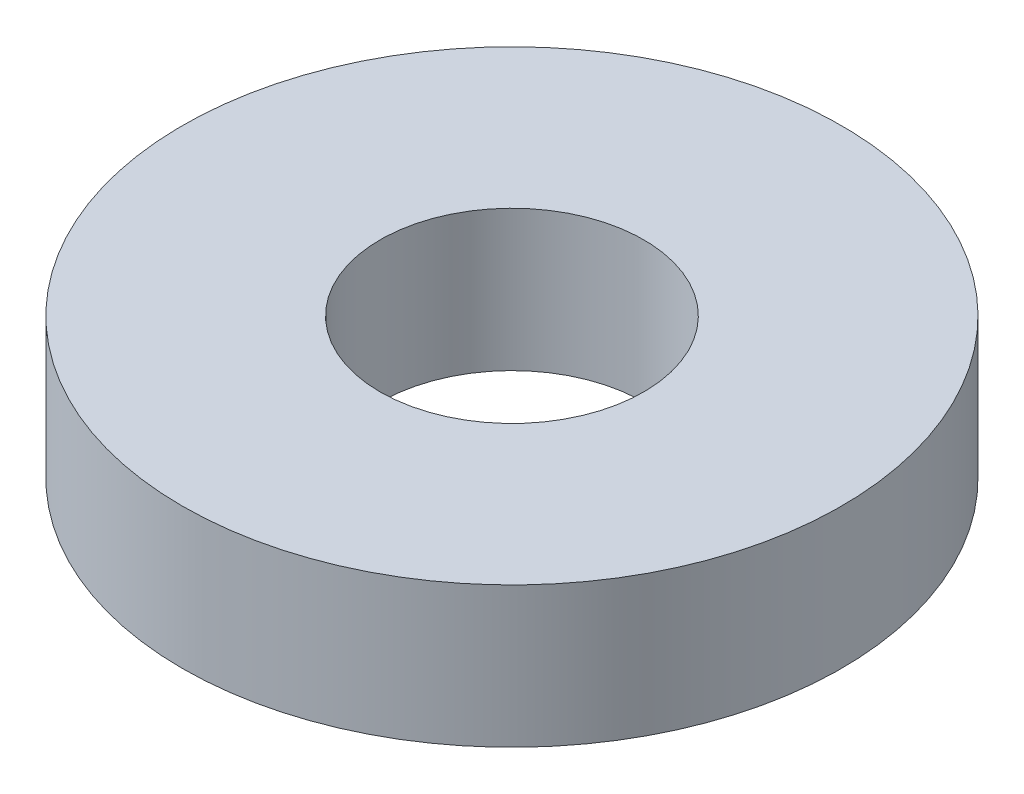
SolidWorks part; units mm, degrees
ref_plane "Front Plane" through (0, 0, 0) normal (0, 0, 1) x (1, 0, 0)
ref_plane "Top Plane" through (0, 0, 0) normal (0, 1, 0) x (1, 0, 0)
ref_plane "Right Plane" through (0, 0, 0) normal (1, 0, 0) x (0, 0, -1)
sketch "Sketch1" plane through (0, 0, 0) normal (0, 1, 0) x (1, 0, 0)
  circle A0 centre (0, 0) radius 37.5
  dimension "FLANGE_OD" = 75
extrude "Boss-Extrude1" add sketch "Sketch1" along normal blind 16
sketch "Sketch2" plane through (0, 0, 0) normal (0, 1, 0) x (1, 0, 0)
  circle A0 centre (0, 0) radius 15
  dimension "BORE_D" = 30
extrude "Cut-Extrude1" cut sketch "Sketch2" along normal through all
sketch "Sketch3" plane through (0, 16, 0) normal (0, 1, 0) x (1, 0, 0)
  circle A0 centre (0, 0) radius 11.5122 construction
  circle A1 centre (-11.5122, 0) radius 2.9986
  dimension "BOLT_D" = 5.9971
  dimension "BOLT_PCD" = 23.0244
extrude "Cut-Extrude2" cut sketch "Sketch3" against normal blind 14.7429 rebuild error yes
pattern_circular "CirPattern1" count 8 over 360 rebuild error yes
